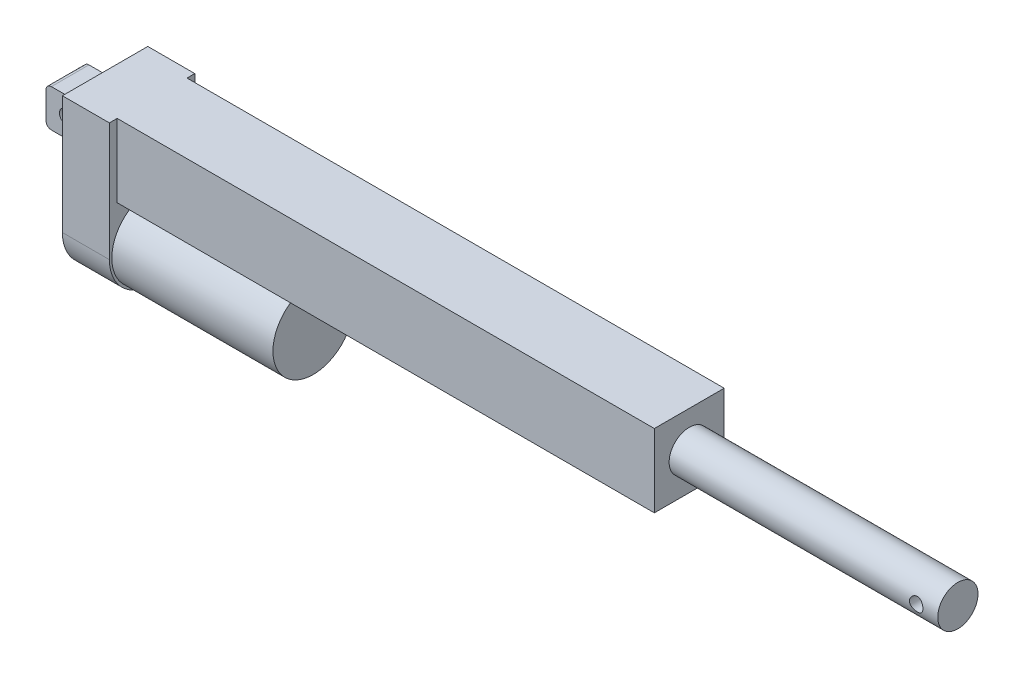
SolidWorks part; units mm, degrees
ref_plane "Front Plane" through (0, 0, 0) normal (0, 0, 1) x (1, 0, 0)
ref_plane "Top Plane" through (0, 0, 0) normal (0, 1, 0) x (1, 0, 0)
ref_plane "Right Plane" through (0, 0, 0) normal (1, 0, 0) x (0, 0, -1)
sketch "Sketch1" plane through (0, 0, 0) normal (1, 0, 0) x (0, 0, -1)
  circle A0 centre (0, 0) radius 9.525
  dimension "D1" = 19.05
extrude "Boss-Extrude1" add sketch "Sketch1" along normal blind 127
sketch "Sketch2" plane through (0, 0, 0) normal (0, 0, 1) x (1, 0, 0)
  line L0 (127, -9.525) -> (127, 9.525) construction
  circle A0 centre (116.84, 0) radius 3.175
  dimension "D1" = 6.35
  dimension "D2" = 10.16
extrude "Cut-Extrude1" cut sketch "Sketch2" against normal through all both and the other way through all
sketch "Sketch3" plane through (0, 0, 0) normal (-1, 0, 0) x (0, 0, 1)
  line L1 (-16.51, 17.272) -> (16.51, 17.272)
  line L2 (-16.51, 17.272) -> (-16.51, -17.272)
  line L3 (-16.51, -17.272) -> (16.51, -17.272)
  line L4 (16.51, 17.272) -> (16.51, -17.272)
  line L5 (-16.51, 17.272) -> (16.51, -17.272) construction
  line L6 (-16.51, -17.272) -> (16.51, 17.272) construction
  point P0 (0, 0)
  dimension "D1" = 34.544
  dimension "D2" = 33.02
extrude "Boss-Extrude2" add sketch "Sketch3" along normal blind 254
sketch "Sketch4" plane through (-254, 0, 0) normal (-1, 0, 0) x (0, 0, 1)
  line L1 (-20.193, 17.272) -> (20.193, 17.272)
  line L2 (-20.193, 17.272) -> (-20.193, -38.735)
  line L4 (20.193, 17.272) -> (20.193, -38.735)
  line L5 (-20.193, 17.272) -> (18.0619, -47.7642) construction
  line L6 (-18.0501, -47.7876) -> (20.193, 17.272) construction
  line L8 (16.51, 17.272) -> (-16.51, 17.272) construction
  arc A1 (-20.193, -38.735) -> (20.193, -38.735) centre (0, -38.735) ccw
  point P0 (0, -9.7283)
  point P1 (0, -58.928)
  point P12 (0, 0)
  point P13 (0, 0)
  point P14 (0, 17.272)
  dimension "D1" = 40.386
  dimension "D2" = 56.007
extrude "Boss-Extrude3" add sketch "Sketch4" along normal blind 22.225
sketch "Sketch5" plane through (-254, 0, 0) normal (1, 0, 0) x (0, 0, -1)
  circle A0 centre (0, -38.735) radius 19.05
  arc A1 (-20.193, -38.735) -> (20.193, -38.735) centre (0, -38.735) ccw construction
  dimension "D1" = 38.1
extrude "Boss-Extrude4" add sketch "Sketch5" along normal blind 76.2
sketch "Sketch6" plane through (0, 0, 0) normal (0, 0, 1) x (1, 0, 0)
  line L0 (-276.225, -38.735) -> (-276.225, 17.272) construction
  line L1 (-276.225, -10.668) -> (-295.275, -10.668)
  line L2 (-276.225, -10.668) -> (-276.225, 7.112)
  line L3 (-276.225, 7.112) -> (-295.275, 7.112)
  line L4 (-295.275, -10.668) -> (-295.275, 7.112)
  line L5 (-276.225, 17.272) -> (-254, 17.272) construction
  line L6 (-295.275, 7.112) -> (-276.225, -10.668) construction
  circle A0 centre (-285.75, -1.778) radius 3.175
  dimension "D4" = 6.35
  dimension "D1" = 10.16
  dimension "D2" = 19.05
  dimension "D3" = 17.78
extrude "Boss-Extrude5" add sketch "Sketch6" along normal mid plane 17.78
fillet "Fillet1" radius 2.54 6 edges at (-276.225, -10.668, 0) (-276.225, -1.778, -8.89) (-276.225, -1.778, 8.89) (-276.225, 7.112, 0) (-295.275, -10.668, 0) (-295.275, 7.112, 0)
